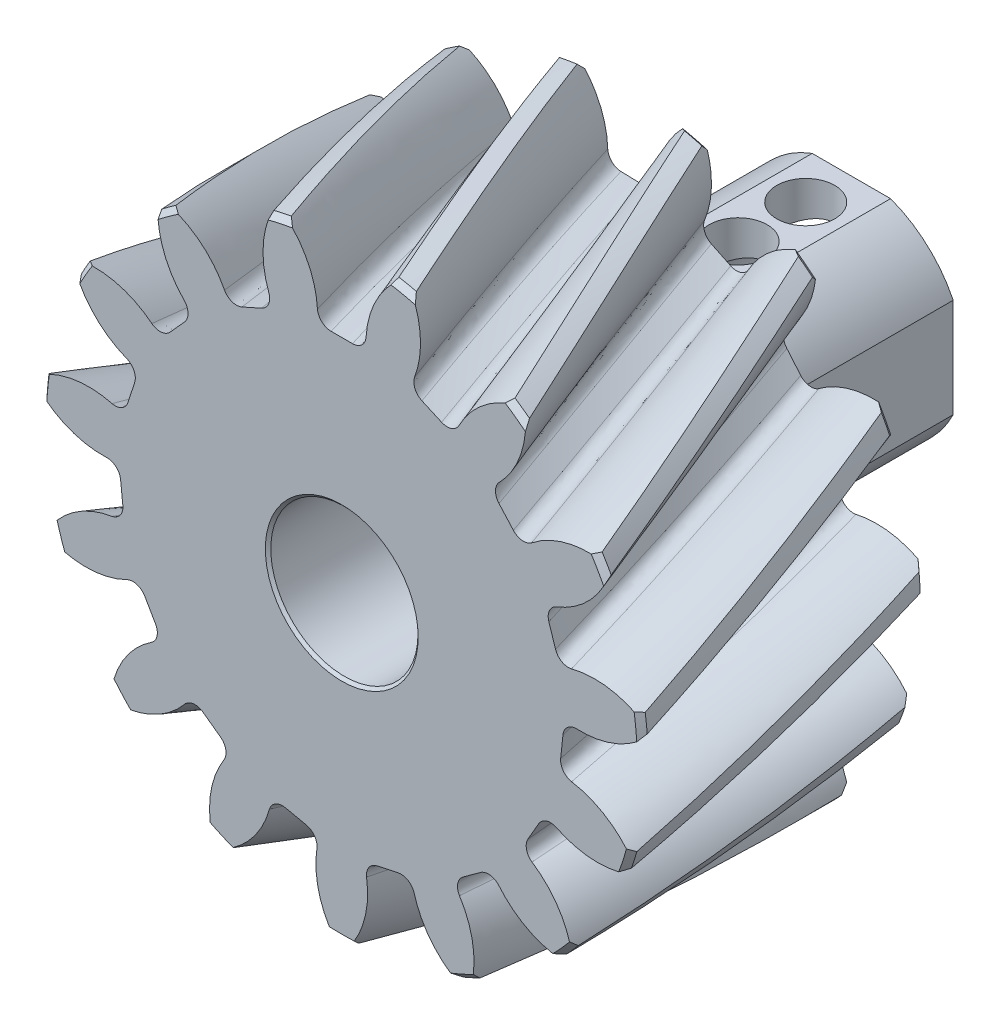
SolidWorks part; units mm, degrees
ref_plane "Front Plane" through (0, 0, 0) normal (0, 0, 1) x (1, 0, 0)
ref_plane "Top Plane" through (0, 0, 0) normal (0, 1, 0) x (1, 0, 0)
ref_plane "Right Plane" through (0, 0, 0) normal (1, 0, 0) x (0, 0, -1)
sketch "Sketch2" plane through (0, 0, 0) normal (0, 0, 1) x (1, 0, 0)
  circle A0 centre (0, 0) radius 10.625
  dimension "D1" = 21.25
extrude "Boss-Extrude1" add sketch "Sketch2" along normal blind 10
hole_wizard "M6 Tapped Hole1" positions "Sketch3" profile "Sketch4" tap size "M6" standard "ISO" end condition through all
sketch "Sketch3" plane through (0, 0, 10) normal (0, 0, 1) x (1, 0, 0)
  point P0 (0, 0)
sketch "Sketch4" plane through (0, 0, 10) normal (1, 0, 0) x (0, -1, 0)
  line L0 (0, 0) -> (0, 10)
  line L1 (0, 10) -> (2.5, 10)
  line L2 (2.5, 10) -> (2.5, 0)
  line L5 (2.5, 0) -> (0, 0)
  line L11 (0, -6.35) -> (0, 107.95) construction
  dimension "Thru Tap Drill Dia." = 5
  dimension "Thru Tap Drill Depth" = 10
chamfer "Chamfer2" distance 0.2 angle 43 4 edges at (10.625, 0, 0) (2.5, 0, 0) (10.625, 0, 10) (2.5, 0, 10) first distance on face at (2.5, 0, 0) first distance on face at (10.625, 0, 10) first distance on face at (2.5, 0, 10)
sketch "Sketch5" plane through (0, 0, 10) normal (0, 0, 1) x (1, 0, 0)
  circle A0 centre (0, 0) radius 10.625
  dimension "D1" = 21.25
curve "Helix/Spiral1" pitch 161.84 height 10 turns 0.0618
sketch "Sketch8" plane through (0, 0, 10) normal (0, 0, 1) x (1, 0, 0)
  line L0 (0, 0) -> (0, 10.625)
  line L1 (-0.38, 7.815) -> (0.38, 7.815)
  arc A0 (1.9, 10.4537) -> (-1.9, 10.4537) centre (0, 0) ccw
  circle A1 centre (0, 0) radius 10.625 construction
  arc A2 (-1.9, 10.4537) -> (-0.8582, 8.2537) centre (-4.1027, 8.064) cw
  arc A3 (-0.8582, 8.2537) -> (-0.38, 7.815) centre (-0.38, 8.295) ccw
  arc A4 (0.8582, 8.2537) -> (0.38, 7.815) centre (0.38, 8.295) cw
  arc A5 (1.9, 10.4537) -> (0.8582, 8.2537) centre (4.1027, 8.064) ccw
  point P14 (0, 7.815)
  dimension "D2" = 3.25
  dimension "D3" = 0.48
  dimension "D1" = 3.8
  dimension "D4" = 2.81
  dimension "D5" = 0.38
  dimension "D6" = 2.2
sweep "Cut-Sweep1" cut profiles "Sketch8" path "Helix/Spiral1" align with end faces yes
sketch "Sketch9" plane through (0, 0, 10) normal (0, 0, 1) x (1, 0, 0)
  circle A0 centre (0, 0) radius 2.6
  dimension "D1" = 5.2
extrude "Cut-Extrude1" cut sketch "Sketch9" against normal blind 10
sketch "Sketch10" plane through (0, 0, 0) normal (0, 0, -1) x (-1, 0, 0)
  line L1 (-3.5964, -3.7527) -> (3.5964, -3.7527)
  line L2 (-3.5964, -3.7527) -> (-3.5964, 3.7527)
  line L3 (-3.5964, 3.7527) -> (3.5964, 3.7527)
  line L4 (3.5964, -3.7527) -> (3.5964, 3.7527)
  line L5 (-3.5964, -3.7527) -> (3.5964, 3.7527) construction
  line L6 (-3.5964, 3.7527) -> (3.5964, -3.7527) construction
  point P0 (0, 0)
  dimension "D1" = 7.1929
extrude "Boss-Extrude2" add sketch "Sketch10" along normal blind 8 contours L2 L1 L4 L3
sketch "Sketch13" plane through (0, 3.7527, 0) normal (0, 1, 0) x (1, 0, 0)
  line L0 (0, 0) -> (0, 8)
  line L1 (3.5964, 8) -> (-3.5964, 8) construction
  line L5 (-0.0079, 0) -> (-0.0079, 6.3958)
  line L6 (3.5964, 0) -> (-3.5964, 0) construction
  line L8 (-3.6123, 6.3958) -> (3.5964, 6.3958)
  line L9 (3.5964, 8) -> (3.5964, 0) construction
  point P13 (0, 4)
  point P56 (-0.0079, 6.3958)
  dimension "D1" = 6.3958
hole_wizard "M2.5 Tapped Hole1" positions "Sketch13" profile "Sketch14" tap size "M2.5" standard "ISO" end condition up to next
sketch "Sketch14" plane through (-0.0079, 3.7527, -6.3958) normal (1, 0, 0) x (0, 0, 1)
  line L0 (0, 0) -> (0, 7.5054)
  line L1 (0, 7.5054) -> (1.025, 7.5054)
  line L2 (1.025, 7.5054) -> (1.025, 0)
  line L5 (1.025, 0) -> (0, 0)
  line L11 (0, -6.35) -> (0, 107.95) construction
  dimension "Thru Tap Drill Dia." = 2.05
  dimension "Thru Tap Drill Depth" = 7.5054
sketch "Sketch19" plane through (3.5964, 0, 0) normal (1, 0, 0) x (0, 0, -1)
  line L0 (0, 0) -> (8, 0)
  line L1 (8, -3.7527) -> (8, 3.7527) construction
  line L2 (4, 3.7527) -> (4, -3.7527)
  line L3 (8, 3.7527) -> (0, 3.7527) construction
  line L4 (8, -3.7527) -> (0, -3.7527) construction
  point P13 (4, 0)
sketch "Sketch25" plane through (0, 0, -8) normal (0, 0, -1) x (-1, 0, 0)
  circle A0 centre (0, 0) radius 2.6
  circle A1 centre (0, 0) radius 4
  dimension "D1" = 5.2
  dimension "D2" = 8
extrude "Cut-Extrude3" cut sketch "Sketch25" against normal blind 17 contours A0
sketch "Sketch26" plane through (0, 0, -8) normal (0, 0, -1) x (-1, 0, 0)
  circle A0 centre (0, 0) radius 4
  circle A1 centre (0, 0) radius 5.8131
  dimension "D1" = 8
extrude "Cut-Extrude4" cut sketch "Sketch26" against normal blind 8
pattern_circular "CirPattern1" count 15 over 360 about axis through (0, 0, 0) along (0, 0, 1) of "Cut-Sweep1" reverse direction yes
